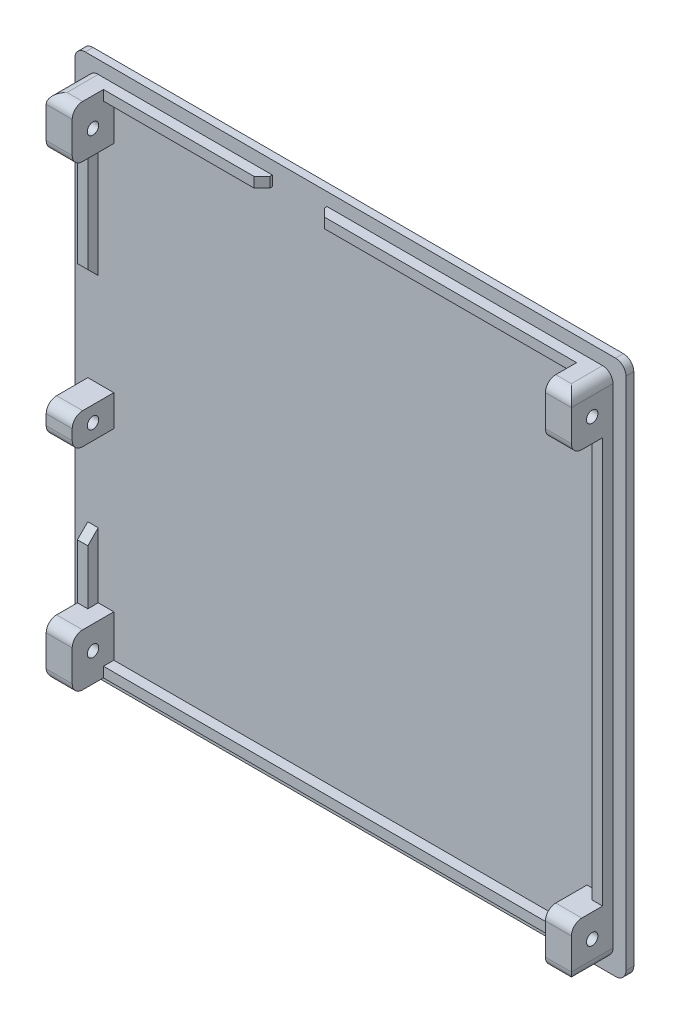
SolidWorks part; units mm, degrees
ref_plane "Спереди" through (0, 0, 0) normal (0, 0, 1) x (1, 0, 0)
ref_plane "Сверху" through (0, 0, 0) normal (0, 1, 0) x (1, 0, 0)
ref_plane "Справа" through (0, 0, 0) normal (1, 0, 0) x (0, 0, -1)
other "Configuration Table"
sketch "Эскиз1" plane through (0, 0, 0) normal (0, 0, 1) x (1, 0, 0)
  line L1 (-53, -51.5) -> (53, -51.5)
  line L2 (-53, -51.5) -> (-53, 51.5)
  line L3 (-53, 51.5) -> (53, 51.5)
  line L4 (53, -51.5) -> (53, 51.5)
  line L5 (-53, -51.5) -> (53, 51.5) construction
  line L6 (-53, 51.5) -> (53, -51.5) construction
  point P0 (0, 0)
  dimension "D1" = 103
  dimension "D2" = 106
extrude "Бобышка-Вытянуть1" add sketch "Эскиз1" along normal blind 1.5
sketch "Эскиз2" plane through (0, 0, 1.5) normal (0, 0, 1) x (1, 0, 0)
  line L0 (-53, 51.5) -> (-53, -51.5) construction
  line L1 (-50.5, -49) -> (50.5, -49)
  line L2 (-50.5, -49) -> (-50.5, 49)
  line L3 (-50.5, 49) -> (50.5, 49)
  line L4 (50.5, -49) -> (50.5, 49)
  line L5 (-50.5, -49) -> (50.5, 49) construction
  line L6 (-50.5, 49) -> (50.5, -49) construction
  line L7 (-48.5, -47.0594) -> (48.5, -47.0594)
  line L8 (-48.5, -47.0594) -> (-48.5, 47.0594)
  line L9 (-48.5, 47.0594) -> (48.5, 47.0594)
  line L10 (48.5, -47.0594) -> (48.5, 47.0594)
  line L11 (-48.5, -47.0594) -> (48.5, 47.0594) construction
  line L12 (-48.5, 47.0594) -> (48.5, -47.0594) construction
  line L13 (-53, -51.5) -> (53, -51.5) construction
  point P0 (0, 0)
  point P6 (0, 0)
  dimension "D1" = 2.5
  dimension "D2" = 2.5
  dimension "D3" = 2
extrude "Бобышка-Вытянуть2" add sketch "Эскиз2" along normal blind 2
sketch "Эскиз3" plane through (0, 0, 1.5) normal (0, 0, 1) x (1, 0, 0)
  line L0 (-50.5, 49) -> (-50.5, -49) construction
  line L1 (-50.5, 49) -> (-45.5, 49)
  line L2 (-50.5, 49) -> (-50.5, 39)
  line L3 (-50.5, 39) -> (-45.5, 39)
  line L4 (-45.5, 49) -> (-45.5, 39)
  line L6 (50.5, 49) -> (-50.5, 49) construction
  line L7 (-48.5, 0) -> (48.5, 0) construction
  line L8 (-48.5, 47.0594) -> (-48.5, -47.0594) construction
  line L9 (48.5, -47.0594) -> (48.5, 47.0594) construction
  line L10 (0, 47.0594) -> (0, -49) construction
  line L11 (48.5, 47.0594) -> (-48.5, 47.0594) construction
  line L12 (-50.5, -49) -> (50.5, -49) construction
  line L13 (45.5, 49) -> (45.5, 39)
  line L14 (50.5, 39) -> (45.5, 39)
  line L15 (50.5, 49) -> (50.5, 39)
  line L16 (50.5, 49) -> (45.5, 49)
  line L17 (50.5, -49) -> (45.5, -49)
  line L18 (50.5, -49) -> (50.5, -39)
  line L19 (50.5, -39) -> (45.5, -39)
  line L20 (45.5, -49) -> (45.5, -39)
  line L21 (-45.5, -49) -> (-45.5, -39)
  line L22 (-50.5, -39) -> (-45.5, -39)
  line L23 (-50.5, -49) -> (-50.5, -39)
  line L24 (-50.5, -49) -> (-45.5, -49)
  dimension "D1" = 5
  dimension "D2" = 10
extrude "Бобышка-Вытянуть3" add sketch "Эскиз3" along normal blind 8
sketch "Эскиз4" plane through (-50.5, 0, 0) normal (-1, 0, 0) x (0, 0, 1)
  line L0 (1.5, 51.5) -> (0, 51.5) construction
  line L1 (1.5, 49) -> (1.5, -49) construction
  line L2 (0, 0) -> (3.5, 0) construction
  line L3 (3.5, 39) -> (3.5, -39) construction
  circle A0 centre (5.5, 43.5) radius 1.1
  circle A1 centre (5.5, -43.5) radius 1.1
  dimension "D3" = 2.2
  dimension "D1" = 8
  dimension "D2" = 4
extrude "Вырез-Вытянуть1" cut sketch "Эскиз4" against normal through all
sketch "Эскиз8" plane through (0, 0, 1.5) normal (0, 0, 1) x (1, 0, 0)
  line L1 (-50.5, -2.5) -> (-45.5, -2.5)
  line L2 (-50.5, -2.5) -> (-50.5, -8.5)
  line L3 (-50.5, -8.5) -> (-45.5, -8.5)
  line L4 (-45.5, -2.5) -> (-45.5, -8.5)
  line L5 (-45.5, 39) -> (-45.5, 49) construction
  line L6 (-53, -51.5) -> (53, -51.5) construction
  line L7 (-50.5, 39) -> (-50.5, -39) construction
  dimension "D1" = 6
  dimension "D2" = 43
extrude "Бобышка-Вытянуть4" add sketch "Эскиз8" along normal up to surface (8 mm away) up to face at (-48, 44, 9.5)
fillet "Скругление1" radius 2 18 edges at (48, 49, 9.5) (48, 39, 9.5) (48, -49, 9.5) (48, -39, 9.5) (-48, -39, 9.5) (-48, -49, 9.5) (-48, 39, 9.5) (-48, 49, 9.5) (-50.5, 49, 5.5) (50.5, 49, 5.5) (50.5, -49, 5.5) (-50.5, -49, 5.5) (-53, -51.5, 0.75) (53, -51.5, 0.75) (53, 51.5, 0.75) (-53, 51.5, 0.75) (-48, -2.5, 9.5) (-48, -8.5, 9.5)
sketch "Эскиз5" plane through (0, 0, 0) normal (0, 0, -1) x (-1, 0, 0)
  line L0 (-13.9595, 39.9554) -> (-13.9595, -38.3885) construction
  text T0 "<b><i>OnStep v_4.24</i></b>" font "Arial" height 8
extrude "Вырез-Вытянуть2" cut sketch "Эскиз5" against normal blind 0.6
sketch "Эскиз6" plane through (0, 0, 0) normal (0, 0, -1) x (-1, 0, 0)
  line L0 (51, -24.5) -> (46, -24.5)
  line L1 (46, -24.5) -> (46, -12.5)
  line L2 (46, -12.5) -> (51, -12.5)
  line L3 (51, -12.5) -> (51, -13.5)
  line L4 (51, -13.5) -> (47, -13.5)
  line L5 (47, -13.5) -> (47, -23.5)
  line L6 (47, -23.5) -> (51, -23.5)
  line L7 (51, -23.5) -> (51, -24.5)
  line L8 (51, -51.5) -> (-51, -51.5) construction
  line L9 (53, 49.5) -> (53, -49.5) construction
  line L10 (51, 1.5) -> (46, 1.5)
  line L11 (46, 1.5) -> (46, 13.5)
  line L12 (46, 13.5) -> (51, 13.5)
  line L13 (51, 13.5) -> (51, 12.5)
  line L14 (51, 12.5) -> (47, 12.5)
  line L15 (47, 12.5) -> (47, 2.5)
  line L16 (47, 2.5) -> (51, 2.5)
  line L17 (51, 2.5) -> (51, 1.5)
  dimension "D1" = 1
  dimension "D2" = 1
  dimension "D3" = 10
  dimension "D4" = 5
  dimension "D5" = 27
  dimension "D6" = 2
  dimension "D7" = 2
extrude "Вырез-Вытянуть3" cut sketch "Эскиз6" against normal blind 0.6
sketch "Эскиз7" plane through (0, 0, 0) normal (0, 0, -1) x (-1, 0, 0)
  line L0 (45, -11.4818) -> (45, -27.4121) construction
  line L1 (45, 2.2558) -> (45, 13.4419) construction
  line L2 (46, -12.5) -> (46, -24.5) construction
  text T0 "<b>RA</b>" font "Arial" height 5
  text T1 "<b>DEC</b>" font "Arial" height 5
  dimension "D1" = 1
extrude "Вырез-Вытянуть4" cut sketch "Эскиз7" against normal blind 0.6
sketch "Эскиз9" plane through (-50.5, 0, 0) normal (-1, 0, 0) x (0, 0, 1)
  line L0 (9.5, -4.5) -> (9.5, -6.5) construction
  line L1 (5.5, 43.5) -> (5.5, -5.5) construction
  circle A0 centre (5.5, -5.5) radius 1.1
  point P4 (9.5, -5.5)
  dimension "D1" = 2.2
extrude "Вырез-Вытянуть5" cut sketch "Эскиз9" against normal up to surface (5 mm away) up to face at (-45.5, -5.5, 6.3047)
ref_axis "Ось1" through (-45.5, -5.5, 5.5) along (-1, 0, 0)
sketch "Эскиз10" plane through (0, 0, 1.5) normal (0, 0, 1) x (1, 0, 0)
  line L0 (-48.5, 39) -> (-48.5, -2.5) construction
  line L1 (-50.5, -2.5) -> (-48.5, -2.5)
  line L2 (-50.5, -2.5) -> (-50.5, 15.5)
  line L3 (-50.5, 15.5) -> (-48.5, 15.5)
  line L4 (-48.5, -2.5) -> (-48.5, 15.5)
  line L5 (-48.5, -8.5) -> (-48.5, -39) construction
  line L6 (-50.5, -8.5) -> (-48.5, -8.5)
  line L7 (-50.5, -8.5) -> (-50.5, -26.5)
  line L8 (-50.5, -26.5) -> (-48.5, -26.5)
  line L9 (-48.5, -8.5) -> (-48.5, -26.5)
  dimension "D1" = 18
extrude "Вырез-Вытянуть6" cut sketch "Эскиз10" along normal up to surface (2 mm away) up to face at (-49.5, 18.25, 3.5)
chamfer "Фаска1" distance 2 angle 45 2 edges at (-49.5, -26.5, 3.5) (-49.5, 15.5, 3.5)
sketch "Эскиз11" plane through (0, 0, 3.5) normal (0, 0, 1) x (1, 0, 0)
  line L0 (45.5, 49) -> (-45.5, 49) construction
  line L1 (-15, 49) -> (-4.5, 49)
  line L2 (-15, 49) -> (-15, 47.0594)
  line L3 (-15, 47.0594) -> (-4.5, 47.0594)
  line L4 (-4.5, 49) -> (-4.5, 47.0594)
  line L5 (45.5, 47.0594) -> (-45.5, 47.0594) construction
  line L6 (-53, 49.5) -> (-53, -49.5) construction
  dimension "D1" = 38
  dimension "D2" = 10.5
extrude "Вырез-Вытянуть7" cut sketch "Эскиз11" against normal up to surface (2 mm away) up to face at (-8.25, -0.9167, 1.5)
chamfer "Фаска2" distance 1.5 angle 45 2 edges at (-15, 48.0297, 3.5) (-4.5, 48.0297, 3.5)
sketch "Эскиз13" [suppressed] plane through (0, 0, 0) normal (0, 0, -1) x (-1, 0, 0)
  line L1 (-51, 51.5) -> (51, 51.5) construction
  line L2 (53, 49.5) -> (53, -49.5) construction
  line L3 (38.9807, 34) -> (53.9807, 34)
  line L5 (38.9807, 33) -> (53.9807, 33)
  line L6 (53.9807, 34) -> (53.9807, 33)
  arc A0 (38.9807, 34) -> (38.9807, 33) centre (32.5, 33.5) ccw
  point P1 (53.9807, 33.5)
  dimension "D1" = 13
  dimension "D2" = 18
  dimension "D3" = 15
  dimension "D4" = 1
  dimension "D5" = 20.5
extrude "Вырез-Вытянуть9" [suppressed] cut sketch "Эскиз13" against normal up to surface (3.5 mm away)
sketch "Эскиз14" [suppressed] plane through (0, 0, 0) normal (0, 0, -1) x (-1, 0, 0)
  line L0 (49.5703, 9.6149) -> (49.5703, -2.6352) construction
  line L1 (49.5703, -13.0336) -> (49.5703, -28.275) construction
  text T0 "<b>DEC</b>" font "Arial" height 5
  text T1 "<b>RA</b>" font "Arial" height 5
extrude "Вырез-Вытянуть10" [suppressed] cut sketch "Эскиз14" against normal blind 0.6
sketch "Эскиз12" [suppressed] plane through (0, 0, 0) normal (0, 0, -1) x (-1, 0, 0)
  line L0 (51, -51.5) -> (-51, -51.5) construction
  line L1 (24.5, -12.5) -> (40.5, -12.5)
  line L2 (24.5, -12.5) -> (24.5, -28.5)
  line L3 (24.5, -28.5) -> (40.5, -28.5)
  line L4 (40.5, -12.5) -> (40.5, -28.5)
  line L5 (53, 49.5) -> (53, 34) construction
  line L6 (-51, 51.5) -> (51, 51.5) construction
  line L7 (24.5, 13.5) -> (40.5, 13.5)
  line L8 (24.5, 13.5) -> (24.5, -2.5)
  line L9 (24.5, -2.5) -> (40.5, -2.5)
  line L10 (40.5, 13.5) -> (40.5, -2.5)
  dimension "D1" = 23
  dimension "D2" = 12.5
  dimension "D3" = 16
  dimension "D4" = 16
  dimension "D5" = 38
extrude "Вырез-Вытянуть8" [suppressed] cut sketch "Эскиз12" against normal up to surface (1.5 mm away)
sketch "Эскиз16" [suppressed] plane through (0, 0, 0) normal (0, 0, -1) x (-1, 0, 0)
  line L0 (53, 33) -> (53, -49.5) construction
  line L1 (24.5, -7.3) -> (40.5, -7.3)
  line L2 (24.5, -7.3) -> (24.5, -23.3)
  line L3 (24.5, -23.3) -> (40.5, -23.3)
  line L4 (40.5, -7.3) -> (40.5, -23.3)
  line L5 (51, -51.5) -> (-51, -51.5) construction
  line L7 (24.5, 18.3) -> (40.5, 18.3)
  line L8 (24.5, 18.3) -> (24.5, 2.3)
  line L9 (24.5, 2.3) -> (40.5, 2.3)
  line L10 (40.5, 18.3) -> (40.5, 2.3)
  dimension "D1" = 12.5
  dimension "D2" = 28.2
  dimension "D3" = 16
  dimension "D4" = 53.8
extrude "Вырез-Вытянуть11" [suppressed] cut sketch "Эскиз16" against normal up to surface (1.5 mm away)
